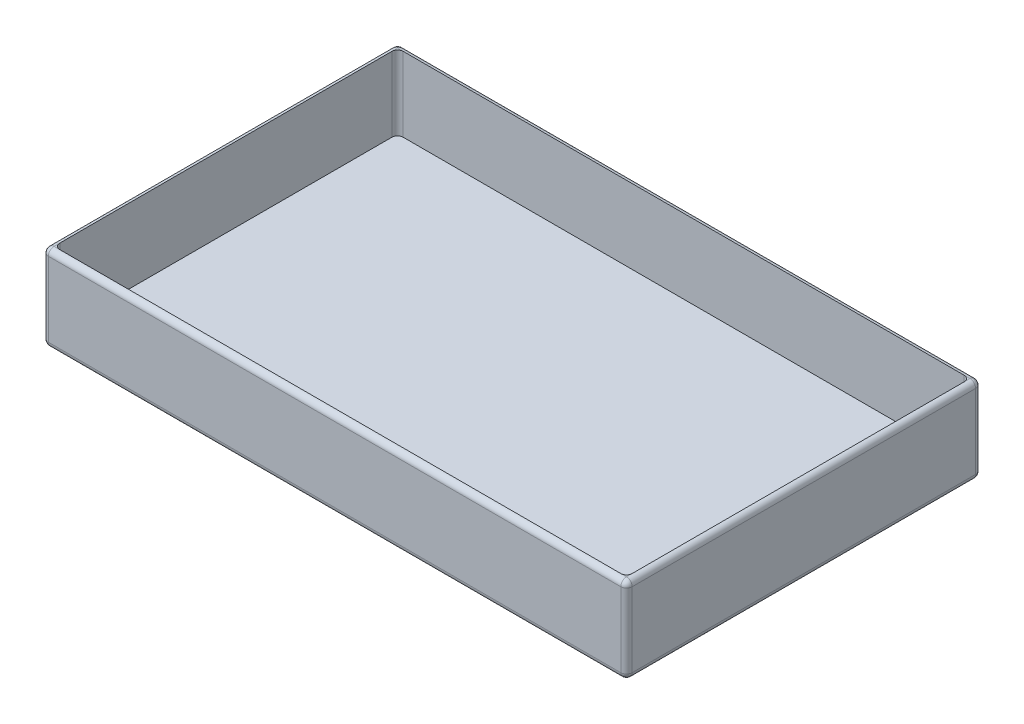
SolidWorks part; units mm, degrees
ref_plane "Front Plane" through (0, 0, 0) normal (0, 0, 1) x (1, 0, 0)
ref_plane "Top Plane" through (0, 0, 0) normal (0, 1, 0) x (1, 0, 0)
ref_plane "Right Plane" through (0, 0, 0) normal (1, 0, 0) x (0, 0, -1)
sketch "Sketch1" plane through (0, 0, 0) normal (0, 1, 0) x (1, 0, 0)
  line L1 (-51, 31) -> (51, 31)
  line L2 (-51, 31) -> (-51, -31)
  line L3 (-51, -31) -> (51, -31)
  line L4 (51, 31) -> (51, -31)
  line L5 (-51, 31) -> (51, -31) construction
  line L6 (-51, -31) -> (51, 31) construction
  point P0 (0, 0)
  dimension "D1" = 62
  dimension "D2" = 102
extrude "Boss-Extrude1" add sketch "Sketch1" along normal blind 15
sketch "Sketch2" plane through (0, 15, 0) normal (0, 1, 0) x (1, 0, 0)
  line L1 (-50, -30) -> (50, -30)
  line L2 (-50, -30) -> (-50, 30)
  line L3 (-50, 30) -> (50, 30)
  line L4 (50, -30) -> (50, 30)
  line L5 (-50, -30) -> (50, 30) construction
  line L6 (-50, 30) -> (50, -30) construction
  point P0 (0, 0)
  dimension "D1" = 100
  dimension "D2" = 60
extrude "Cut-Extrude1" cut sketch "Sketch2" against normal blind 13
fillet "Fillet2" radius 1 4 edges at (50, 8.5, -30) (-50, 8.5, -30) (-50, 8.5, 30) (50, 8.5, 30)
fillet "Fillet3" radius 1 12 edges at (51, 15, 0) (0, 15, 31) (51, 7.5, 31) (-51, 15, 0) (-51, 7.5, 31) (51, 7.5, -31) (0, 15, -31) (-51, 7.5, -31) (0, 0, -31) (-51, 0, 0) (0, 0, 31) (51, 0, 0)
